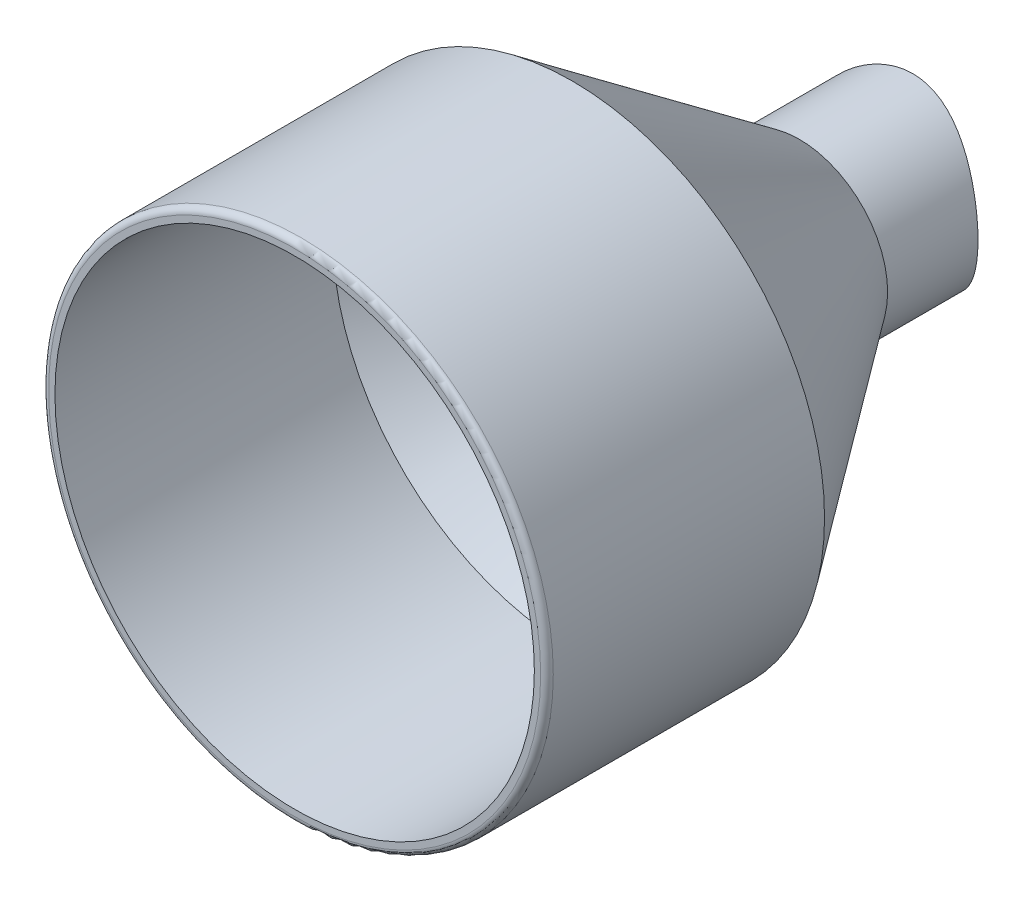
SolidWorks part; units mm, degrees
ref_plane "Front Plane" through (0, 0, 0) normal (0, 0, 1) x (1, 0, 0)
ref_plane "Top Plane" through (0, 0, 0) normal (0, 1, 0) x (1, 0, 0)
ref_plane "Right Plane" through (0, 0, 0) normal (1, 0, 0) x (0, 0, -1)
sketch "Sketch1" plane through (0, 0, 0) normal (0, 0, 1) x (1, 0, 0)
  circle A0 centre (0, 0) radius 20
  circle A1 centre (0, 0) radius 19
  dimension "D1" = 40
  dimension "D2" = 1
extrude "Boss-Extrude1" add sketch "Sketch1" along normal blind 22
sketch "Sketch2" plane through (0, 0, 0) normal (0, 0, -1) x (-1, 0, 0)
  circle A0 centre (0, 0) radius 20 construction
  point P0 (0, 0)
  point P1 (0, 20)
sketch "Sketch4" plane through (0, 0, 22) normal (0, 0, 1) x (1, 0, 0)
  point P0 (0, 20)
ref_plane "Plane1" through (0, 0, 0) normal (1, 0, 0) x (0, 0, -1)
sketch "Sketch5" plane through (0, 0, 0) normal (1, 0, 0) x (0, 0, -1)
  line L0 (0, 0) -> (30, 0) construction
  line L3 (18, 7) -> (0, 20)
  line L4 (0, -20) -> (0, 20) construction
  line L5 (0, 20) -> (0, 19)
  line L6 (0, 19) -> (18, 6)
  line L7 (18, 6) -> (18, 7)
  line L10 (18, 7) -> (27, 7)
  line L11 (18, 7) -> (18, 6)
  line L12 (18, 6) -> (27, 6)
  line L13 (27, 7) -> (27, 6)
  point P2 (0, 0)
  dimension "D1" = 18
  dimension "D2" = 9
  dimension "D3" = 6
  dimension "D4" = 1
fillet "Fillet1" radius 0.5 1 edges at (20, 0, 22)
revolve "Revolve1" add sketch "Sketch5" angle 360 about L0 region at (0, 13, -9) region at (0, 6.5, -22.5)
sketch "Sketch6" plane through (0, 0, 0) normal (1, 0, 0) x (0, 0, -1)
  line L2 (27, 7) -> (27, -7) construction
  circle A0 centre (39.4122, 0) radius 14.25
  point P5 (27, 0)
  dimension "D1" = 28.5
extrude "Cut-Extrude1" cut sketch "Sketch6" against normal blind 10 and the other way blind 10
sketch "Sketch7" plane through (0, 0, 22) normal (0, 0, 1) x (1, 0, 0)
  line L1 (-5, -1) -> (-7, -1)
  line L2 (-5, -1) -> (-5, 1)
  line L3 (-5, 1) -> (-7, 1)
  line L4 (-7, -1) -> (-7, 1)
  line L5 (-5, -1) -> (-7, 1) construction
  line L6 (-5, 1) -> (-7, -1) construction
  line L7 (5, -1) -> (7, -1)
  line L8 (5, -1) -> (5, 1)
  line L9 (5, 1) -> (7, 1)
  line L10 (7, -1) -> (7, 1)
  line L11 (5, -1) -> (7, 1) construction
  line L12 (5, 1) -> (7, -1) construction
  circle A0 centre (0, 0) radius 7 construction
  circle A1 centre (0, 0) radius 7
  point P0 (-6, 0)
  point P5 (6, 0)
  dimension "D1" = 2
  dimension "D2" = 2
  dimension "D3" = 2
  dimension "D4" = 2
extrude "Boss-Extrude2" add sketch "Sketch7" against normal blind 4 from offset 40 contours L3 A1 L1 L2 | A1 L9 L8 L7 region at (-5.9882, 0, 22) region at (5.9882, 0, 22) offset against normal yes
chamfer "Chamfer1" distance 1 angle 45 2 edges at (-5, 0, -22) (5, 0, -22)
